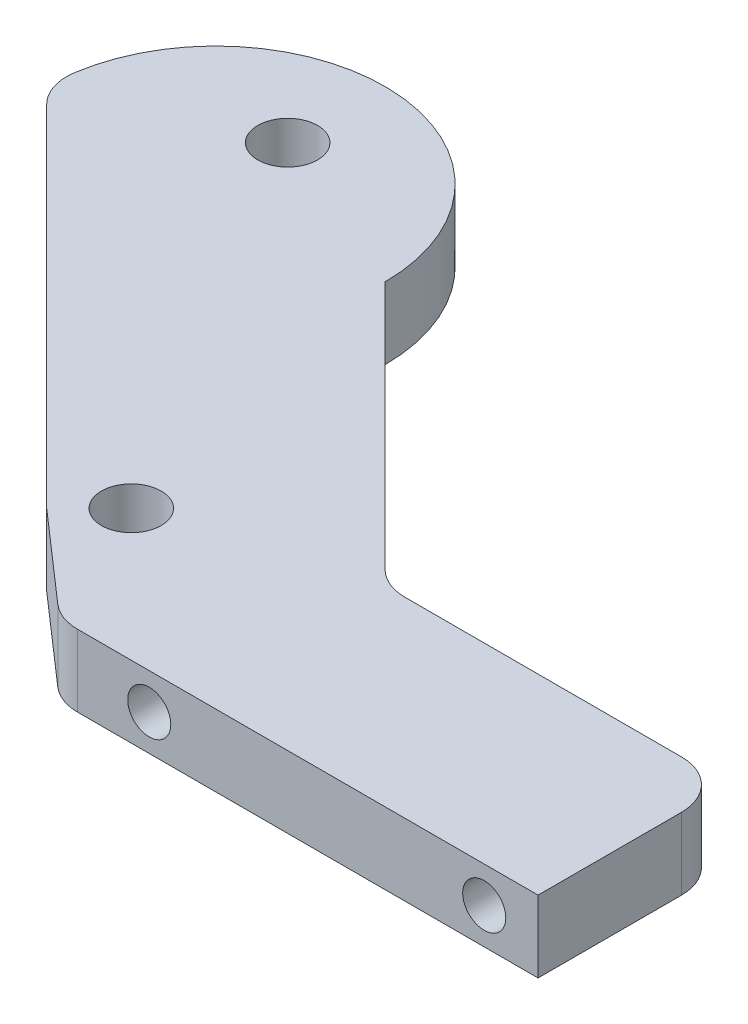
SolidWorks part; units mm, degrees
ref_plane "Front Plane" through (0, 0, 0) normal (0, 0, 1) x (1, 0, 0)
ref_plane "Top Plane" through (0, 0, 0) normal (0, 1, 0) x (1, 0, 0)
ref_plane "Right Plane" through (0, 0, 0) normal (1, 0, 0) x (0, 0, -1)
sketch "Sketch1" plane through (0, 0, 0) normal (0, 1, 0) x (1, 0, 0)
  line L0 (0, 6.35) -> (12.3665, 6.35)
  line L1 (12.3665, 6.35) -> (57.15, 6.35)
  line L2 (6.35, 0) -> (6.35, -13.97)
  line L3 (6.35, -13.97) -> (57.15, -13.97)
  line L4 (57.15, 6.35) -> (57.15, -13.97)
  line L5 (20.5908, 6.35) -> (-7.3492, 34.29)
  line L6 (-4.4901, -4.4901) -> (-43.2703, 34.29)
  line L7 (-4.4901, -4.4901) -> (6.35, -13.97)
  circle A0 centre (0, 0) radius 3.175
  arc A1 (0, 6.35) -> (6.35, 0) centre (0, 0) ccw
  arc A2 (-43.2703, 34.29) -> (-7.3492, 34.29) centre (-25.3097, 34.29) cw
  dimension "D1" = 12.7
  dimension "D2" = 6.35
  dimension "D3" = 6.35
  dimension "D4" = 50.8
  dimension "D5" = 20.32
  dimension "D6" = 45
  dimension "D7" = 25.4
  dimension "D8" = 27.94
extrude "Boss-Extrude1" add sketch "Sketch1" along normal mid plane 7.62 contours A2 L6 A1 L0 L1 L5 | L0 A1 L2 L3 L4 L1 A0 | A1 L7 L2 region at (-15.7867, 0, -26.7963) region at (28.8904, 0, 3.4247) region at (3.6646, 0, 8.0416)
sketch "Sketch2" plane through (0, 0, 13.97) normal (0, 0, 1) x (1, 0, 0)
  circle A0 centre (51.4379, 0) radius 1.8987 construction
  circle A1 centre (15.8779, 0) radius 1.8987 construction
  circle A2 centre (51.4379, 0) radius 1.8986
  circle A3 centre (15.8779, 0) radius 1.8987
  circle A4 centre (15.8779, 0) radius 2.286
  circle A5 centre (51.4379, 0) radius 2.286
  dimension "D1" = 4.572
  dimension "D2" = 4.572
extrude "Cut-Extrude1" cut sketch "Sketch2" against normal blind 5.08 contours A4 | A5 | A3 | A2 region at (51.4379, 0, 13.97) region at (15.8779, 0, 13.97) region at (13.6566, 0, 13.97) region at (49.2166, 0, 13.97)
fillet "Fillet1" radius 5.08 4 edges at (57.15, 0, -6.35) (20.5908, 0, -6.35) (6.35, 0, 13.97) (-43.2703, 0, -34.29)
sketch "Sketch3" plane through (0, 3.81, 0) normal (0, 1, 0) x (1, 0, 0)
  circle A0 centre (-25.3097, 41.91) radius 3.175
  arc A1 (-7.3492, 34.29) -> (-43.0622, 37.016) centre (-25.3097, 34.29) ccw construction
  arc A2 (-7.3492, 34.29) -> (-43.0622, 37.016) centre (-25.3097, 34.29) ccw
  point P5 (0, 0)
  dimension "D2" = 6.35
  dimension "D1" = 7.62
extrude "Cut-Extrude2" cut sketch "Sketch3" against normal through all contours A0 region at (-25.3097, 3.81, -41.91)
